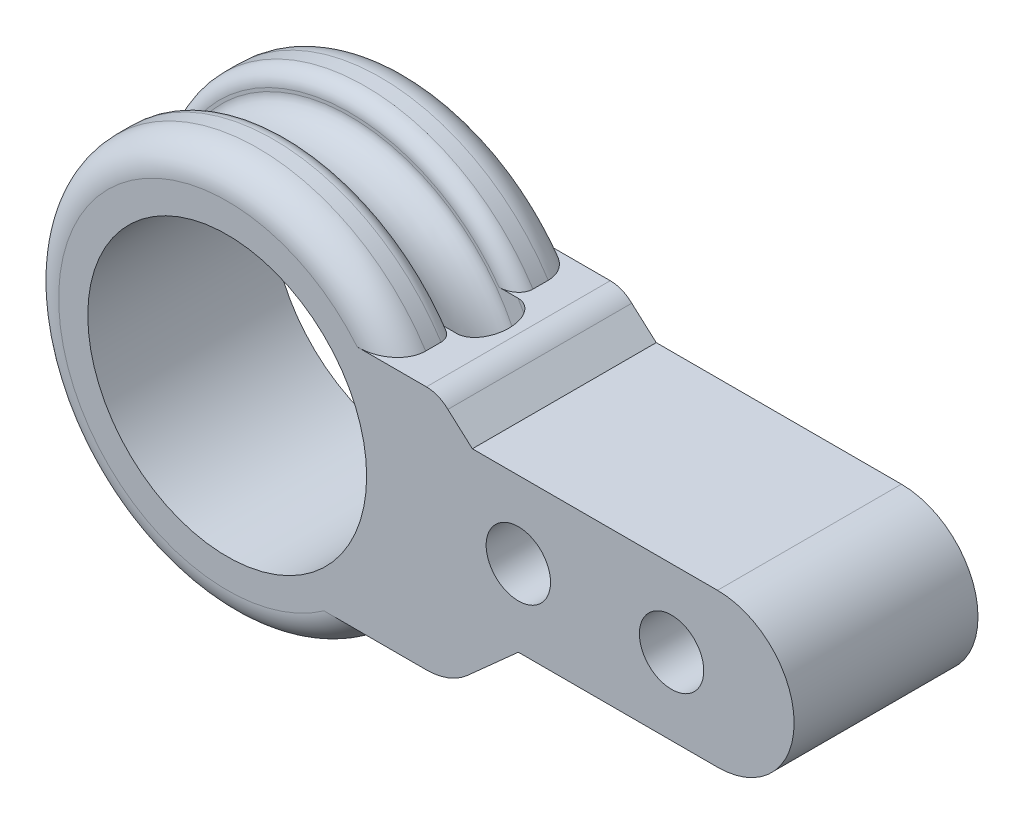
SolidWorks part; units mm, degrees
ref_plane "Front Plane" through (0, 0, 0) normal (0, 0, 1) x (1, 0, 0)
ref_plane "Top Plane" through (0, 0, 0) normal (0, 1, 0) x (1, 0, 0)
ref_plane "Right Plane" through (0, 0, 0) normal (1, 0, 0) x (0, 0, -1)
sketch "Sketch1" plane through (0, 0, 0) normal (0, 0, 1) x (1, 0, 0)
  line L0 (-8.6467, 0) -> (4.55, 0) construction
  line L1 (6.5, -4.5) -> (11.498, -4.5) construction
  line L2 (9.5, -2.5) -> (16, -2.5)
  line L4 (8, 2.5) -> (16, 2.5)
  line L6 (11.498, -4.5) -> (0, -4.5) construction
  line L7 (4.6904, -4.5) -> (6.5, -4.5)
  line L8 (9.5, -2.5) -> (7.8333, -3.9907)
  line L9 (6.5, 3.5) -> (5.4772, 3.5)
  line L10 (8, 2.5) -> (7.2011, 3.213)
  line L11 (18.5, 0) -> (18.5, 5.2131) construction
  line L12 (18.5, 5.2131) -> (18.5, -3.7014) construction
  line L13 (18.5, 0) -> (4.55, 0) construction
  line L14 (4.55, 0) -> (18.5, 0) construction
  circle A0 centre (0, 0) radius 4.55
  arc A2 (6.5, -4.5) -> (7.8333, -3.9907) centre (6.5, -2.5) ccw
  arc A3 (7.2011, 3.213) -> (6.5, 3.5) centre (6.5, 2.5) ccw
  arc A4 (16, -2.5) -> (16, 2.5) centre (16, 0) ccw
  arc A5 (6.5, -0.5) -> (6.4807, -0.5001) centre (6.5, -2.5) ccw
  arc A6 (5.4772, 3.5) -> (4.6904, -4.5) centre (0, 0) ccw
  circle A7 centre (14.5, 0) radius 1.05
  circle A8 centre (9.5, 0) radius 1.05
  point P13 (4.6904, -4.5)
  point P16 (9.5, -2.5)
  point P22 (8, 2.5)
  dimension "D1" = 9.1
  dimension "D2" = 2.1
  dimension "D6" = 4
  dimension "D7" = 3
  dimension "D8" = 2
  dimension "D4" = 2.1
  dimension "D3" = 4
  dimension "D5" = 5
  dimension "D9" = 1.5
extrude "Boss-Extrude1" add sketch "Sketch1" along normal blind 6 contours A2 L8 L2 A4 L4 L10 A3 L9 A6 L7
extrude "Cut-Extrude2" cut sketch "Sketch1<5>" along normal through all contours A0
sketch "Sketch1<5>" plane through (0, 0, 0) normal (0, 0, 1) x (1, 0, 0) same geometry as "Sketch1"
extrude "Cut-Extrude3" cut sketch "Sketch1<6>" along normal through all contours A7 | A8
sketch "Sketch1<6>" plane through (0, 0, 0) normal (0, 0, 1) x (1, 0, 0) same geometry as "Sketch1"
sketch "Sketch5" plane through (0, 0, 0) normal (1, 0, 0) x (0, 0, -1)
  line L0 (-6.97, 0) -> (1.8664, 0) construction
  line L18 (-3.9984, 6.509) -> (-3.9984, 5.899)
  line L23 (-1.9984, 5.899) -> (-1.9984, 6.509)
  line L24 (-2.9984, 7.6936) -> (-2.9984, 4.6386) construction
  line L28 (0, 6.5) -> (-6, 6.5) construction
  line L29 (-1.9984, 5.299) -> (-4.023, 5.299) construction
  line L30 (-1.9984, 6.509) -> (-3.9984, 6.509) construction
  line L31 (-1.9984, 6.204) -> (-3.9984, 6.204) construction
  ellipse E0 centre (-2.9984, 5.899) end of major axis (-3.9984, 5.899) minor radius 0.6 (-3.9984, 5.899) -> (-1.9984, 5.899) ccw
  ellipse E1 centre (-2.9984, 6.509) end of major axis (-3.9984, 6.509) minor radius 0.6 (-3.9984, 6.509) -> (-1.9984, 6.509) cw
  point P8 (-2.9984, 6.509)
  dimension "D1" = 0.61
revolve "Cut-Revolve2" cut sketch "Sketch5" angle 360 about L0
fillet "Fillet1" radius 1 2 edges at (-6.4688, 0.6362, 6) (-6.4688, 0.6362, 0)
fillet "Fillet3" radius 0.5 2 edges at (-6.4688, 0.6362, 1.9984) (-6.4688, 0.6362, 3.9984)
